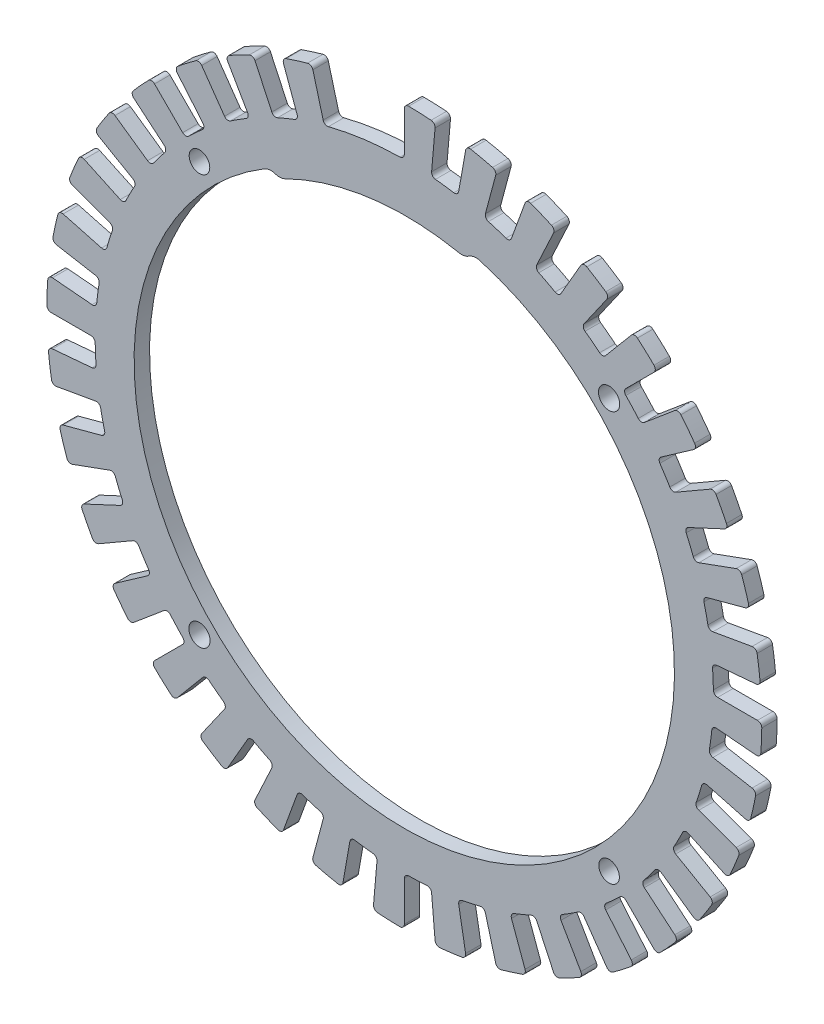
SolidWorks part; units mm, degrees
ref_plane "Front Plane" through (0, 0, 0) normal (0, 0, 1) x (1, 0, 0)
ref_plane "Top Plane" through (0, 0, 0) normal (0, 1, 0) x (1, 0, 0)
ref_plane "Right Plane" through (0, 0, 0) normal (1, 0, 0) x (0, 0, -1)
sketch "Sketch1" plane through (0, 0, 0) normal (0, 0, 1) x (1, 0, 0)
  line L0 (0, 82.7) -> (0, 71.5) construction
  line L1 (7.2078, 82.3853) -> (6.2316, 71.2279) construction
  line L2 (0, 71.5) -> (0, 0) construction
  line L3 (6.2316, 71.2279) -> (0, 0) construction
  line L4 (12.5883, 71.3918) -> (14.186, 80.4528) construction
  line L5 (12.5883, 71.3918) -> (0, 0) construction
  line L8 (0, 0) -> (47.3762, 47.3762) construction
  line L12 (50.5581, 50.5581) -> (47.3762, 47.3762) construction
  line L15 (47.3762, 47.3762) -> (44.1942, 44.1942) construction
  line L18 (7.3144, 72.1301) -> (6.3182, 72.2172) construction
  line L21 (7.3144, 72.1301) -> (7.2135, 71.1352) construction
  line L24 (12.5883, 71.3918) -> (11.6035, 71.5654) construction
  line L27 (11.6035, 71.5654) -> (11.4434, 70.5783) construction
  line L30 (1.0122, 82.6938) -> (1, 81.6939) construction
  line L33 (1, 81.6939) -> (0, 81.6939) construction
  line L36 (7.1201, 81.383) -> (6.1239, 81.4702) construction
  line L39 (6.1239, 81.4702) -> (6.1989, 82.4674) construction
  line L42 (7.1201, 81.383) -> (6.3182, 72.2172)
  line L45 (0, 81.6939) -> (0, 72.4931)
  line L48 (0, 72.4931) -> (-1, 72.4931) construction
  line L51 (-1, 72.4931) -> (-0.9862, 71.4932) construction
  line L109 (0, -82.7) -> (0, -71.5) [skipped]
  line L111 (14.3607, 81.4436) -> (12.4158, 70.4138) [skipped]
  line L115 (41.35, 71.6203) -> (35.75, 61.9208) [skipped]
  line L117 (53.1585, 63.3519) -> (45.9593, 54.7722) [skipped]
  line L118 (-63.3519, -53.1585) -> (-54.7722, -45.9593) [skipped]
  line L119 (63.3519, 53.1585) -> (54.7722, 45.9593) [skipped]
  line L121 (71.6203, 41.35) -> (61.9208, 35.75) [skipped]
  line L123 (77.7126, 28.2851) -> (67.188, 24.4544) [skipped]
  line L125 (81.4436, 14.3607) -> (70.4138, 12.4158) [skipped]
  line L127 (82.7, 0) -> (71.5, 0) [skipped]
  line L129 (81.4436, -14.3607) -> (70.4138, -12.4158) [skipped]
  line L131 (77.7126, -28.2851) -> (67.188, -24.4544) [skipped]
  line L133 (71.6203, -41.35) -> (61.9208, -35.75) [skipped]
  line L135 (63.3519, -53.1585) -> (54.7722, -45.9593) [skipped]
  line L137 (53.1585, -63.3519) -> (45.9593, -54.7722) [skipped]
  line L139 (41.35, -71.6203) -> (35.75, -61.9208) [skipped]
  line L141 (28.2851, -77.7126) -> (24.4544, -67.188) [skipped]
  line L142 (14.3607, -81.4436) -> (12.4158, -70.4138) [skipped]
  line L143 (34.9505, 74.9517) -> (30.2172, 64.801) [skipped]
  line L144 (47.4348, 67.7439) -> (41.0107, 58.5694) [skipped]
  line L145 (58.4777, 58.4777) -> (50.5581, 50.5581) [skipped]
  line L146 (67.7439, 47.4348) -> (58.5694, 41.0107) [skipped]
  line L147 (74.9517, 34.9505) -> (64.801, 30.2172) [skipped]
  line L148 (79.8821, 21.4043) -> (69.0637, 18.5056) [skipped]
  line L149 (82.3853, 7.2078) -> (71.2279, 6.2316) [skipped]
  line L150 (82.3853, -7.2078) -> (71.2279, -6.2316) [skipped]
  line L151 (79.8821, -21.4043) -> (69.0637, -18.5056) [skipped]
  line L152 (74.9517, -34.9505) -> (64.801, -30.2172) [skipped]
  line L153 (67.7439, -47.4348) -> (58.5694, -41.0107) [skipped]
  line L154 (58.4777, -58.4777) -> (50.5581, -50.5581) [skipped]
  line L155 (47.4348, -67.7439) -> (41.0107, -58.5694) [skipped]
  line L156 (34.9505, -74.9517) -> (30.2172, -64.801) [skipped]
  line L157 (21.4043, -79.8821) -> (18.5056, -69.0637) [skipped]
  line L158 (7.2078, -82.3853) -> (6.2316, -71.2279) [skipped]
  line L159 (-7.2078, -82.3853) -> (-6.2316, -71.2279) [skipped]
  line L160 (-21.4043, -79.8821) -> (-18.5056, -69.0637) [skipped]
  line L161 (-34.9505, -74.9517) -> (-30.2172, -64.801) [skipped]
  line L162 (-47.4348, -67.7439) -> (-41.0107, -58.5694) [skipped]
  line L163 (-58.4777, -58.4777) -> (-50.5581, -50.5581) [skipped]
  line L164 (-67.7439, -47.4348) -> (-58.5694, -41.0107) [skipped]
  line L165 (-74.9517, -34.9505) -> (-64.801, -30.2172) [skipped]
  line L166 (-79.8821, -21.4043) -> (-69.0637, -18.5056) [skipped]
  line L167 (-82.3853, -7.2078) -> (-71.2279, -6.2316) [skipped]
  line L168 (-82.3853, 7.2078) -> (-71.2279, 6.2316) [skipped]
  line L169 (-79.8821, 21.4043) -> (-69.0637, 18.5056) [skipped]
  line L170 (-74.9517, 34.9505) -> (-64.801, 30.2172) [skipped]
  line L171 (-67.7439, 47.4348) -> (-58.5694, 41.0107) [skipped]
  line L172 (-58.4777, 58.4777) -> (-50.5581, 50.5581) [skipped]
  line L173 (-47.4348, 67.7439) -> (-41.0107, 58.5694) [skipped]
  line L174 (-34.9505, 74.9517) -> (-30.2172, 64.801) [skipped]
  line L175 (-21.4043, 79.8821) -> (-18.5056, 69.0637) [skipped]
  line L176 (21.4043, 79.8821) -> (18.5056, 69.0637) [skipped]
  line L209 (0, 0) -> (-47.3762, -47.3762) construction
  line L210 (0, 0) -> (-47.3762, 47.3762) construction
  line L211 (0, 0) -> (47.3762, -47.3762) construction
  line L212 (14.186, 80.4528) -> (12.5883, 71.3918)
  line L213 (21.1439, 78.9102) -> (18.7626, 70.023)
  line L214 (27.941, 76.7671) -> (24.7941, 68.1212)
  line L215 (34.5253, 74.0398) -> (30.6369, 65.7011)
  line L216 (40.8469, 70.749) -> (36.2466, 62.7809)
  line L217 (46.8577, 66.9197) -> (41.5803, 59.3829)
  line L218 (52.5118, 62.5811) -> (46.5977, 55.5329)
  line L219 (57.7663, 57.7663) -> (51.2604, 51.2604)
  line L220 (62.5811, 52.5118) -> (55.5329, 46.5977)
  line L221 (66.9197, 46.8577) -> (59.3829, 41.5803)
  line L222 (70.749, 40.8469) -> (62.7809, 36.2466)
  line L223 (74.0398, 34.5253) -> (65.7011, 30.6369)
  line L224 (76.7671, 27.941) -> (68.1212, 24.7941)
  line L225 (78.9102, 21.1439) -> (70.023, 18.7626)
  line L226 (80.4528, 14.186) -> (71.3918, 12.5883)
  line L227 (81.383, 7.1201) -> (72.2172, 6.3182)
  line L228 (81.6939, 0) -> (72.4931, 0)
  line L229 (81.383, -7.1201) -> (72.2172, -6.3182)
  line L230 (80.4528, -14.186) -> (71.3918, -12.5883)
  line L231 (78.9102, -21.1439) -> (70.023, -18.7626)
  line L232 (76.7671, -27.941) -> (68.1212, -24.7941)
  line L233 (74.0398, -34.5253) -> (65.7011, -30.6369)
  line L234 (70.749, -40.8469) -> (62.7809, -36.2466)
  line L235 (66.9197, -46.8577) -> (59.3829, -41.5803)
  line L236 (62.5811, -52.5118) -> (55.5329, -46.5977)
  line L237 (57.7663, -57.7663) -> (51.2604, -51.2604)
  line L238 (52.5118, -62.5811) -> (46.5977, -55.5329)
  line L239 (46.8577, -66.9197) -> (41.5803, -59.3829)
  line L240 (40.8469, -70.749) -> (36.2466, -62.7809)
  line L241 (34.5253, -74.0398) -> (30.6369, -65.7011)
  line L242 (27.941, -76.7671) -> (24.7941, -68.1212)
  line L243 (21.1439, -78.9102) -> (18.7626, -70.023)
  line L244 (14.186, -80.4528) -> (12.5883, -71.3918)
  line L245 (7.1201, -81.383) -> (6.3182, -72.2172)
  line L246 (0, -81.6939) -> (0, -72.4931)
  line L247 (-7.1201, -81.383) -> (-6.3182, -72.2172)
  line L248 (-14.186, -80.4528) -> (-12.5883, -71.3918)
  line L249 (-21.1439, -78.9102) -> (-18.7626, -70.023)
  line L250 (-27.941, -76.7671) -> (-24.7941, -68.1212)
  line L251 (-34.5253, -74.0398) -> (-30.6369, -65.7011)
  line L252 (-40.8469, -70.749) -> (-36.2466, -62.7809)
  line L253 (-46.8577, -66.9197) -> (-41.5803, -59.3829)
  line L254 (-52.5118, -62.5811) -> (-46.5977, -55.5329)
  line L255 (-57.7663, -57.7663) -> (-51.2604, -51.2604)
  line L256 (-62.5811, -52.5118) -> (-55.5329, -46.5977)
  line L257 (-66.9197, -46.8577) -> (-59.3829, -41.5803)
  line L258 (-70.749, -40.8469) -> (-62.7809, -36.2466)
  line L259 (-74.0398, -34.5253) -> (-65.7011, -30.6369)
  line L260 (-76.7671, -27.941) -> (-68.1212, -24.7941)
  line L261 (-78.9102, -21.1439) -> (-70.023, -18.7626)
  line L262 (-80.4528, -14.186) -> (-71.3918, -12.5883)
  line L263 (-81.383, -7.1201) -> (-72.2172, -6.3182)
  line L264 (-81.6939, 0) -> (-72.4931, 0)
  line L265 (-81.383, 7.1201) -> (-72.2172, 6.3182)
  line L266 (-80.4528, 14.186) -> (-71.3918, 12.5883)
  line L267 (-78.9102, 21.1439) -> (-70.023, 18.7626)
  line L268 (-76.7671, 27.941) -> (-68.1212, 24.7941)
  line L269 (-74.0398, 34.5253) -> (-65.7011, 30.6369)
  line L270 (-70.749, 40.8469) -> (-62.7809, 36.2466)
  line L271 (-66.9197, 46.8577) -> (-59.3829, 41.5803)
  line L272 (-62.5811, 52.5118) -> (-55.5329, 46.5977)
  line L273 (-57.7663, 57.7663) -> (-51.2604, 51.2604)
  line L274 (-52.5118, 62.5811) -> (-46.5977, 55.5329)
  line L275 (-46.8577, 66.9197) -> (-41.5803, 59.3829)
  line L276 (-40.8469, 70.749) -> (-36.2466, 62.7809)
  line L277 (-34.5253, 74.0398) -> (-30.6369, 65.7011)
  line L278 (-27.941, 76.7671) -> (-24.7941, 68.1212)
  line L279 (-21.1439, 78.9102) -> (-18.7626, 70.023)
  line L280 (-0.9864, 71.4932) -> (-0.9862, 71.4932)
  line L281 (-32.3995, 53.4464) -> (-30.8444, 50.881) construction
  line L282 (-30.8444, 50.881) -> (-29.8635, 53.7161) construction
  line L283 (-29.8635, 53.7161) -> (-28.8826, 56.5512) construction
  line L284 (-28.8826, 56.5512) -> (-27.5181, 53.8795) construction
  line L285 (17.4626, 60.0109) -> (16.6244, 57.1304) construction
  line L286 (16.6244, 57.1304) -> (14.9432, 59.615) construction
  line L289 (13.262, 62.0997) -> (14.9432, 59.615) construction
  line L290 (-7.4414, 56.5227) -> (0, 0) construction
  line L291 (-27.5181, 53.8795) -> (-7.4414, 56.5227) construction
  line L292 (-7.4414, 56.5227) -> (12.6354, 59.1658) construction
  line L293 (13.262, 62.0997) -> (12.6354, 59.1658) construction
  line L294 (-28.4278, 55.6607) -> (13.0531, 61.1217) construction
  circle A0 centre (0, 0) radius 82.7 construction
  arc A1 (-32.3995, 53.4464) -> (17.4626, 60.0109) centre (0, 0) ccw
  circle A73 centre (47.3762, 47.3762) radius 2.4585
  circle A74 centre (47.3762, 47.3762) radius 2.987 construction
  arc A78 (0, 71.5) -> (6.2316, 71.2279) centre (0, 0) cw construction
  arc A79 (6.3182, 72.2172) -> (7.2135, 71.1352) centre (7.3144, 72.1301) ccw
  arc A80 (11.4434, 70.5783) -> (12.5883, 71.3918) centre (11.6035, 71.5654) ccw construction
  arc A81 (7.1201, 81.383) -> (6.1989, 82.4674) centre (6.1239, 81.4702) ccw
  arc A82 (0, 81.6939) -> (1.0122, 82.6938) centre (1, 81.6939) cw
  arc A83 (6.5367, 74.7146) -> (13.0236, 73.8606) centre (0, 0) cw [skipped]
  arc A84 (7.2135, 71.1352) -> (11.4434, 70.5783) centre (0, 0) cw
  arc A85 (0, 82.7) -> (7.2078, 82.3853) centre (0, 0) cw [skipped]
  arc A86 (1.0122, 82.6938) -> (6.1989, 82.4674) centre (0, 0) cw
  arc A87 (28.2851, 77.7126) -> (34.9505, 74.9517) centre (0, 0) cw [skipped]
  arc A88 (31.6964, 67.9731) -> (37.5, 64.9519) centre (0, 0) cw [skipped]
  arc A89 (41.35, 71.6203) -> (47.4348, 67.7439) centre (0, 0) cw [skipped]
  arc A90 (43.0182, 61.4364) -> (48.2091, 57.4533) centre (0, 0) cw [skipped]
  arc A91 (53.1585, 63.3519) -> (58.4777, 58.4777) centre (0, 0) cw [skipped]
  arc A92 (53.033, 53.033) -> (57.4533, 48.2091) centre (0, 0) cw [skipped]
  arc A93 (63.3519, 53.1585) -> (67.7439, 47.4348) centre (0, 0) cw [skipped]
  arc A94 (61.4364, 43.0182) -> (64.9519, 37.5) centre (0, 0) cw [skipped]
  arc A95 (71.6203, 41.35) -> (74.9517, 34.9505) centre (0, 0) cw [skipped]
  arc A96 (67.9731, 31.6964) -> (70.4769, 25.6515) centre (0, 0) cw [skipped]
  arc A97 (77.7126, 28.2851) -> (79.8821, 21.4043) centre (0, 0) cw [skipped]
  arc A98 (72.4444, 19.4114) -> (73.8606, 13.0236) centre (0, 0) cw [skipped]
  arc A99 (81.4436, 14.3607) -> (82.3853, 7.2078) centre (0, 0) cw [skipped]
  arc A100 (74.7146, 6.5367) -> (75, 0) centre (0, 0) cw [skipped]
  arc A101 (82.7, 0) -> (82.3853, -7.2078) centre (0, 0) cw [skipped]
  arc A102 (74.7146, -6.5367) -> (73.8606, -13.0236) centre (0, 0) cw [skipped]
  arc A103 (81.4436, -14.3607) -> (79.8821, -21.4043) centre (0, 0) cw [skipped]
  arc A104 (72.4444, -19.4114) -> (70.4769, -25.6515) centre (0, 0) cw [skipped]
  arc A105 (77.7126, -28.2851) -> (74.9517, -34.9505) centre (0, 0) cw [skipped]
  arc A106 (67.9731, -31.6964) -> (64.9519, -37.5) centre (0, 0) cw [skipped]
  arc A107 (71.6203, -41.35) -> (67.7439, -47.4348) centre (0, 0) cw [skipped]
  arc A108 (61.4364, -43.0182) -> (57.4533, -48.2091) centre (0, 0) cw [skipped]
  arc A109 (63.3519, -53.1585) -> (58.4777, -58.4777) centre (0, 0) cw [skipped]
  arc A110 (53.033, -53.033) -> (48.2091, -57.4533) centre (0, 0) cw [skipped]
  arc A111 (53.1585, -63.3519) -> (47.4348, -67.7439) centre (0, 0) cw [skipped]
  arc A112 (43.0182, -61.4364) -> (37.5, -64.9519) centre (0, 0) cw [skipped]
  arc A113 (41.35, -71.6203) -> (34.9505, -74.9517) centre (0, 0) cw [skipped]
  arc A114 (31.6964, -67.9731) -> (25.6515, -70.4769) centre (0, 0) cw [skipped]
  arc A115 (28.2851, -77.7126) -> (21.4043, -79.8821) centre (0, 0) cw [skipped]
  arc A116 (19.4114, -72.4444) -> (13.0236, -73.8606) centre (0, 0) cw [skipped]
  arc A117 (14.3607, -81.4436) -> (7.2078, -82.3853) centre (0, 0) cw [skipped]
  arc A118 (6.5367, -74.7146) -> (0, -75) centre (0, 0) cw [skipped]
  arc A119 (0, -82.7) -> (-7.2078, -82.3853) centre (0, 0) cw [skipped]
  arc A120 (-6.5367, -74.7146) -> (-13.0236, -73.8606) centre (0, 0) cw [skipped]
  arc A121 (-14.3607, -81.4436) -> (-21.4043, -79.8821) centre (0, 0) cw [skipped]
  arc A122 (-28.2851, -77.7126) -> (-34.9505, -74.9517) centre (0, 0) cw [skipped]
  arc A123 (-19.4114, -72.4444) -> (-25.6515, -70.4769) centre (0, 0) cw [skipped]
  arc A124 (-31.6964, -67.9731) -> (-37.5, -64.9519) centre (0, 0) cw [skipped]
  arc A125 (-41.35, -71.6203) -> (-47.4348, -67.7439) centre (0, 0) cw [skipped]
  arc A126 (-43.0182, -61.4364) -> (-48.2091, -57.4533) centre (0, 0) cw [skipped]
  arc A127 (-53.1585, -63.3519) -> (-58.4777, -58.4777) centre (0, 0) cw [skipped]
  arc A128 (-53.033, -53.033) -> (-57.4533, -48.2091) centre (0, 0) cw [skipped]
  arc A129 (-63.3519, -53.1585) -> (-67.7439, -47.4348) centre (0, 0) cw [skipped]
  arc A130 (-61.4364, -43.0182) -> (-64.9519, -37.5) centre (0, 0) cw [skipped]
  arc A131 (-71.6203, -41.35) -> (-74.9517, -34.9505) centre (0, 0) cw [skipped]
  arc A132 (-67.9731, -31.6964) -> (-70.4769, -25.6515) centre (0, 0) cw [skipped]
  arc A133 (-77.7126, -28.2851) -> (-79.8821, -21.4043) centre (0, 0) cw [skipped]
  arc A134 (-72.4444, -19.4114) -> (-73.8606, -13.0236) centre (0, 0) cw [skipped]
  arc A135 (-81.4436, -14.3607) -> (-82.3853, -7.2078) centre (0, 0) cw [skipped]
  arc A136 (-74.7146, -6.5367) -> (-75, 0) centre (0, 0) cw [skipped]
  arc A137 (-82.7, 0) -> (-82.3853, 7.2078) centre (0, 0) cw [skipped]
  arc A138 (-74.7146, 6.5367) -> (-73.8606, 13.0236) centre (0, 0) cw [skipped]
  arc A139 (-81.4436, 14.3607) -> (-79.8821, 21.4043) centre (0, 0) cw [skipped]
  arc A140 (-72.4444, 19.4114) -> (-70.4769, 25.6515) centre (0, 0) cw [skipped]
  arc A141 (-77.7126, 28.2851) -> (-74.9517, 34.9505) centre (0, 0) cw [skipped]
  arc A142 (-67.9731, 31.6964) -> (-64.9519, 37.5) centre (0, 0) cw [skipped]
  arc A143 (-71.6203, 41.35) -> (-67.7439, 47.4348) centre (0, 0) cw [skipped]
  arc A144 (-61.4364, 43.0182) -> (-57.4533, 48.2091) centre (0, 0) cw [skipped]
  arc A145 (-63.3519, 53.1585) -> (-58.4777, 58.4777) centre (0, 0) cw [skipped]
  arc A146 (-53.033, 53.033) -> (-48.2091, 57.4533) centre (0, 0) cw [skipped]
  arc A147 (-53.1585, 63.3519) -> (-47.4348, 67.7439) centre (0, 0) cw [skipped]
  arc A148 (-43.0182, 61.4364) -> (-37.5, 64.9519) centre (0, 0) cw [skipped]
  arc A149 (-41.35, 71.6203) -> (-34.9505, 74.9517) centre (0, 0) cw [skipped]
  arc A150 (-31.6964, 67.9731) -> (-25.6515, 70.4769) centre (0, 0) cw [skipped]
  arc A151 (-28.2851, 77.7126) -> (-21.4043, 79.8821) centre (0, 0) cw [skipped]
  arc A152 (-19.4114, 72.4444) -> (-13.0236, 73.8606) centre (0, 0) cw [skipped]
  arc A153 (14.3607, 81.4436) -> (21.4043, 79.8821) centre (0, 0) cw [skipped]
  arc A154 (19.4114, 72.4444) -> (25.6515, 70.4769) centre (0, 0) cw [skipped]
  arc A155 (0, 72.4931) -> (-0.9862, 71.4932) centre (-1, 72.4931) cw
  circle A367 centre (-47.3762, -47.3762) radius 2.4585
  circle A368 centre (47.3762, -47.3762) radius 2.3812
  circle A369 centre (-47.3762, 47.3762) radius 2.3813
  circle A370 centre (0, 0) radius 71.5 construction
  arc A371 (12.5883, 71.3918) -> (11.4434, 70.5783) centre (11.6035, 71.5654) cw
  arc A372 (14.186, 80.4528) -> (15.3565, 81.2617) centre (15.1708, 80.2791) cw
  arc A373 (15.3565, 81.2617) -> (20.425, 80.1381) centre (0, 0) cw
  arc A374 (21.1439, 78.9102) -> (20.425, 80.1381) centre (20.178, 79.169) ccw
  arc A375 (18.7626, 70.023) -> (19.4564, 68.8019) centre (19.7285, 69.7641) ccw
  arc A376 (19.4564, 68.8019) -> (23.5254, 67.5189) centre (0, 0) cw
  arc A377 (24.7941, 68.1212) -> (23.5254, 67.5189) centre (23.8544, 68.4633) cw
  arc A378 (27.941, 76.7671) -> (29.2341, 77.3606) centre (28.8806, 76.4251) cw
  arc A379 (29.2341, 77.3606) -> (34.0305, 75.3738) centre (0, 0) cw
  arc A380 (34.5253, 74.0398) -> (34.0305, 75.3738) centre (33.619, 74.4624) ccw
  arc A381 (30.6369, 65.7011) -> (31.1081, 64.3781) centre (31.5432, 65.2784) ccw
  arc A382 (31.1081, 64.3781) -> (34.8925, 62.408) centre (0, 0) cw
  arc A384 (36.2466, 62.7809) -> (34.8925, 62.408) centre (35.3805, 63.2809) cw
  arc A385 (40.8469, 70.749) -> (42.2235, 71.1088) centre (41.713, 70.249) cw
  arc A386 (42.2235, 71.1088) -> (46.602, 68.3194) centre (0, 0) cw
  arc A387 (46.8577, 66.9197) -> (46.602, 68.3194) centre (46.0385, 67.4933) ccw
  arc A388 (41.5803, 59.3829) -> (41.8147, 57.9981) centre (42.3995, 58.8093) ccw
  arc A389 (41.8147, 57.9981) -> (45.1995, 55.4009) centre (0, 0) cw
  arc A390 (46.5977, 55.5329) -> (45.1995, 55.4009) centre (45.8316, 56.1757) cw
  arc A391 (52.5118, 62.5811) -> (53.93, 62.6965) centre (53.2779, 61.9384) cw
  arc A392 (53.93, 62.6965) -> (57.7576, 59.1891) centre (0, 0) cw
  arc A393 (57.7663, 57.7663) -> (57.7576, 59.1891) centre (57.0592, 58.4734) ccw
  arc A394 (51.2604, 51.2604) -> (51.2507, 49.856) centre (51.9675, 50.5533) ccw
  arc A395 (51.2507, 49.856) -> (54.133, 46.7104) centre (0, 0) cw
  arc A396 (55.5329, 46.5977) -> (54.133, 46.7104) centre (54.8902, 47.3637) cw
  arc A397 (62.5811, 52.5118) -> (63.9978, 52.3791) centre (63.2239, 51.7458) cw
  arc A398 (63.9978, 52.3791) -> (67.1582, 48.2604) centre (0, 0) cw
  arc A399 (66.9197, 46.8577) -> (67.1582, 48.2604) centre (66.3461, 47.6768) ccw
  arc A400 (59.3829, 41.5803) -> (59.1295, 40.199) centre (59.9565, 40.7612) ccw
  arc A401 (59.1295, 40.199) -> (61.4218, 36.6007) centre (0, 0) cw
  arc A402 (62.7809, 36.2466) -> (61.4218, 36.6007) centre (62.2809, 37.1126) cw
  arc A403 (70.749, 40.8469) -> (72.1211, 40.4703) centre (71.249, 39.9809) cw
  arc A404 (72.1211, 40.4703) -> (74.5182, 35.8653) centre (0, 0) cw
  arc A405 (74.0398, 34.5253) -> (74.5182, 35.8653) centre (73.6172, 35.4316) ccw
  arc A406 (65.7011, 30.6369) -> (65.2116, 29.3205) centre (66.1237, 29.7306) ccw
  arc A407 (65.2116, 29.3205) -> (66.8443, 25.3788) centre (0, 0) cw
  arc A408 (68.1212, 24.7941) -> (66.8443, 25.3788) centre (67.7792, 25.7338) cw
  arc A409 (76.7671, 27.941) -> (78.053, 27.3318) centre (77.1092, 27.0013) cw
  arc A410 (78.053, 27.3318) -> (79.6141, 22.3805) centre (0, 0) cw
  arc A411 (78.9102, 21.1439) -> (79.6141, 22.3805) centre (78.6514, 22.1099) ccw
  arc A412 (70.023, 18.7626) -> (69.3124, 17.5512) centre (70.2818, 17.7967) ccw
  arc A413 (69.3124, 17.5512) -> (70.2358, 13.3859) centre (0, 0) cw
  arc A414 (71.3918, 12.5883) -> (70.2358, 13.3859) centre (71.2181, 13.5731) cw
  arc A415 (80.4528, 14.186) -> (81.6133, 13.3628) centre (80.6264, 13.2012) cw
  arc A416 (81.6133, 13.3628) -> (82.2909, 8.2156) centre (0, 0) cw
  arc A417 (81.383, 7.1201) -> (82.2909, 8.2156) centre (81.2959, 8.1163) ccw
  arc A418 (72.2172, 6.3182) -> (71.3071, 5.2486) centre (72.3044, 5.322) ccw
  arc A419 (71.3071, 5.2486) -> (71.4932, 0.9862) centre (0, 0) cw
  arc A420 (72.4931, 0) -> (71.4932, 0.9862) centre (72.4931, 1) cw
  arc A421 (81.6939, 0) -> (82.6938, -1.0122) centre (81.6939, -1) cw
  arc A422 (82.6938, -1.0122) -> (82.4674, -6.1989) centre (0, 0) cw
  arc A423 (81.383, -7.1201) -> (82.4674, -6.1989) centre (81.4702, -6.1239) ccw
  arc A424 (72.2172, -6.3182) -> (71.1352, -7.2135) centre (72.1301, -7.3144) ccw
  arc A425 (71.1352, -7.2135) -> (70.5783, -11.4434) centre (0, 0) cw
  arc A426 (71.3918, -12.5883) -> (70.5783, -11.4434) centre (71.5654, -11.6035) cw
  arc A427 (80.4528, -14.186) -> (81.2617, -15.3565) centre (80.2791, -15.1708) cw
  arc A428 (81.2617, -15.3565) -> (80.1381, -20.425) centre (0, 0) cw
  arc A429 (78.9102, -21.1439) -> (80.1381, -20.425) centre (79.169, -20.178) ccw
  arc A430 (70.023, -18.7626) -> (68.8019, -19.4564) centre (69.7641, -19.7285) ccw
  arc A431 (68.8019, -19.4564) -> (67.5189, -23.5254) centre (0, 0) cw
  arc A432 (68.1212, -24.7941) -> (67.5189, -23.5254) centre (68.4633, -23.8544) cw
  arc A433 (76.7671, -27.941) -> (77.3606, -29.2341) centre (76.4251, -28.8806) cw
  arc A434 (77.3606, -29.2341) -> (75.3738, -34.0305) centre (0, 0) cw
  arc A435 (74.0398, -34.5253) -> (75.3738, -34.0305) centre (74.4624, -33.619) ccw
  arc A436 (65.7011, -30.6369) -> (64.3781, -31.1081) centre (65.2784, -31.5432) ccw
  arc A437 (64.3781, -31.1081) -> (62.408, -34.8925) centre (0, 0) cw
  arc A438 (62.7809, -36.2466) -> (62.408, -34.8925) centre (63.2809, -35.3805) cw
  arc A439 (70.749, -40.8469) -> (71.1088, -42.2235) centre (70.249, -41.713) cw
  arc A440 (71.1088, -42.2235) -> (68.3194, -46.602) centre (0, 0) cw
  arc A441 (66.9197, -46.8577) -> (68.3194, -46.602) centre (67.4933, -46.0385) ccw
  arc A442 (59.3829, -41.5803) -> (57.9981, -41.8147) centre (58.8093, -42.3995) ccw
  arc A443 (57.9981, -41.8147) -> (55.4009, -45.1995) centre (0, 0) cw
  arc A444 (55.5329, -46.5977) -> (55.4009, -45.1995) centre (56.1757, -45.8316) cw
  arc A445 (62.5811, -52.5118) -> (62.6965, -53.93) centre (61.9384, -53.2779) cw
  arc A446 (62.6965, -53.93) -> (59.1891, -57.7576) centre (0, 0) cw
  arc A447 (57.7663, -57.7663) -> (59.1891, -57.7576) centre (58.4734, -57.0592) ccw
  arc A448 (51.2604, -51.2604) -> (49.856, -51.2507) centre (50.5533, -51.9675) ccw
  arc A449 (49.856, -51.2507) -> (46.7104, -54.133) centre (0, 0) cw
  arc A450 (46.5977, -55.5329) -> (46.7104, -54.133) centre (47.3637, -54.8902) cw
  arc A451 (52.5118, -62.5811) -> (52.3791, -63.9978) centre (51.7458, -63.2239) cw
  arc A452 (52.3791, -63.9978) -> (48.2604, -67.1582) centre (0, 0) cw
  arc A453 (46.8577, -66.9197) -> (48.2604, -67.1582) centre (47.6768, -66.3461) ccw
  arc A454 (41.5803, -59.3829) -> (40.199, -59.1295) centre (40.7612, -59.9565) ccw
  arc A455 (40.199, -59.1295) -> (36.6007, -61.4218) centre (0, 0) cw
  arc A456 (36.2466, -62.7809) -> (36.6007, -61.4218) centre (37.1126, -62.2809) cw
  arc A457 (40.8469, -70.749) -> (40.4703, -72.1211) centre (39.9809, -71.249) cw
  arc A458 (40.4703, -72.1211) -> (35.8653, -74.5182) centre (0, 0) cw
  arc A459 (34.5253, -74.0398) -> (35.8653, -74.5182) centre (35.4316, -73.6172) ccw
  arc A460 (30.6369, -65.7011) -> (29.3205, -65.2116) centre (29.7306, -66.1237) ccw
  arc A461 (29.3205, -65.2116) -> (25.3788, -66.8443) centre (0, 0) cw
  arc A462 (24.7941, -68.1212) -> (25.3788, -66.8443) centre (25.7338, -67.7792) cw
  arc A463 (27.941, -76.7671) -> (27.3318, -78.053) centre (27.0013, -77.1092) cw
  arc A464 (27.3318, -78.053) -> (22.3805, -79.6141) centre (0, 0) cw
  arc A465 (21.1439, -78.9102) -> (22.3805, -79.6141) centre (22.1099, -78.6514) ccw
  arc A466 (18.7626, -70.023) -> (17.5512, -69.3124) centre (17.7967, -70.2818) ccw
  arc A467 (17.5512, -69.3124) -> (13.3859, -70.2358) centre (0, 0) cw
  arc A468 (12.5883, -71.3918) -> (13.3859, -70.2358) centre (13.5731, -71.2181) cw
  arc A469 (14.186, -80.4528) -> (13.3628, -81.6133) centre (13.2012, -80.6264) cw
  arc A470 (13.3628, -81.6133) -> (8.2156, -82.2909) centre (0, 0) cw
  arc A471 (7.1201, -81.383) -> (8.2156, -82.2909) centre (8.1163, -81.2959) ccw
  arc A472 (6.3182, -72.2172) -> (5.2486, -71.3071) centre (5.322, -72.3044) ccw
  arc A473 (5.2486, -71.3071) -> (0.9862, -71.4932) centre (0, 0) cw
  arc A474 (0, -72.4931) -> (0.9862, -71.4932) centre (1, -72.4931) cw
  arc A475 (0, -81.6939) -> (-1.0122, -82.6938) centre (-1, -81.6939) cw
  arc A476 (-1.0122, -82.6938) -> (-6.1989, -82.4674) centre (0, 0) cw
  arc A477 (-7.1201, -81.383) -> (-6.1989, -82.4674) centre (-6.1239, -81.4702) ccw
  arc A478 (-6.3182, -72.2172) -> (-7.2135, -71.1352) centre (-7.3144, -72.1301) ccw
  arc A479 (-7.2135, -71.1352) -> (-11.4434, -70.5783) centre (0, 0) cw
  arc A480 (-12.5883, -71.3918) -> (-11.4434, -70.5783) centre (-11.6035, -71.5654) cw
  arc A481 (-14.186, -80.4528) -> (-15.3565, -81.2617) centre (-15.1708, -80.2791) cw
  arc A482 (-15.3565, -81.2617) -> (-20.425, -80.1381) centre (0, 0) cw
  arc A483 (-21.1439, -78.9102) -> (-20.425, -80.1381) centre (-20.178, -79.169) ccw
  arc A484 (-18.7626, -70.023) -> (-19.4564, -68.8019) centre (-19.7285, -69.7641) ccw
  arc A485 (-19.4564, -68.8019) -> (-23.5254, -67.5189) centre (0, 0) cw
  arc A486 (-24.7941, -68.1212) -> (-23.5254, -67.5189) centre (-23.8544, -68.4633) cw
  arc A487 (-27.941, -76.7671) -> (-29.2341, -77.3606) centre (-28.8806, -76.4251) cw
  arc A488 (-29.2341, -77.3606) -> (-34.0305, -75.3738) centre (0, 0) cw
  arc A489 (-34.5253, -74.0398) -> (-34.0305, -75.3738) centre (-33.619, -74.4624) ccw
  arc A490 (-30.6369, -65.7011) -> (-31.1081, -64.3781) centre (-31.5432, -65.2784) ccw
  arc A491 (-31.1081, -64.3781) -> (-34.8925, -62.408) centre (0, 0) cw
  arc A492 (-36.2466, -62.7809) -> (-34.8925, -62.408) centre (-35.3805, -63.2809) cw
  arc A493 (-40.8469, -70.749) -> (-42.2235, -71.1088) centre (-41.713, -70.249) cw
  arc A494 (-42.2235, -71.1088) -> (-46.602, -68.3194) centre (0, 0) cw
  arc A495 (-46.8577, -66.9197) -> (-46.602, -68.3194) centre (-46.0385, -67.4933) ccw
  arc A496 (-41.5803, -59.3829) -> (-41.8147, -57.9981) centre (-42.3995, -58.8093) ccw
  arc A497 (-41.8147, -57.9981) -> (-45.1995, -55.4009) centre (0, 0) cw
  arc A498 (-46.5977, -55.5329) -> (-45.1995, -55.4009) centre (-45.8316, -56.1757) cw
  arc A499 (-52.5118, -62.5811) -> (-53.93, -62.6965) centre (-53.2779, -61.9384) cw
  arc A500 (-53.93, -62.6965) -> (-57.7576, -59.1891) centre (0, 0) cw
  arc A501 (-57.7663, -57.7663) -> (-57.7576, -59.1891) centre (-57.0592, -58.4734) ccw
  arc A502 (-51.2604, -51.2604) -> (-51.2507, -49.856) centre (-51.9675, -50.5533) ccw
  arc A503 (-51.2507, -49.856) -> (-54.133, -46.7104) centre (0, 0) cw
  arc A504 (-55.5329, -46.5977) -> (-54.133, -46.7104) centre (-54.8902, -47.3637) cw
  arc A505 (-62.5811, -52.5118) -> (-63.9978, -52.3791) centre (-63.2239, -51.7458) cw
  arc A506 (-63.9978, -52.3791) -> (-67.1582, -48.2604) centre (0, 0) cw
  arc A507 (-66.9197, -46.8577) -> (-67.1582, -48.2604) centre (-66.3461, -47.6768) ccw
  arc A508 (-59.3829, -41.5803) -> (-59.1295, -40.199) centre (-59.9565, -40.7612) ccw
  arc A509 (-59.1295, -40.199) -> (-61.4218, -36.6007) centre (0, 0) cw
  arc A510 (-62.7809, -36.2466) -> (-61.4218, -36.6007) centre (-62.2809, -37.1126) cw
  arc A511 (-70.749, -40.8469) -> (-72.1211, -40.4703) centre (-71.249, -39.9809) cw
  arc A512 (-72.1211, -40.4703) -> (-74.5182, -35.8653) centre (0, 0) cw
  arc A513 (-74.0398, -34.5253) -> (-74.5182, -35.8653) centre (-73.6172, -35.4316) ccw
  arc A514 (-65.7011, -30.6369) -> (-65.2116, -29.3205) centre (-66.1237, -29.7306) ccw
  arc A515 (-65.2116, -29.3205) -> (-66.8443, -25.3788) centre (0, 0) cw
  arc A516 (-68.1212, -24.7941) -> (-66.8443, -25.3788) centre (-67.7792, -25.7338) cw
  arc A517 (-76.7671, -27.941) -> (-78.053, -27.3318) centre (-77.1092, -27.0013) cw
  arc A518 (-78.053, -27.3318) -> (-79.6141, -22.3805) centre (0, 0) cw
  arc A519 (-78.9102, -21.1439) -> (-79.6141, -22.3805) centre (-78.6514, -22.1099) ccw
  arc A520 (-70.023, -18.7626) -> (-69.3124, -17.5512) centre (-70.2818, -17.7967) ccw
  arc A521 (-69.3124, -17.5512) -> (-70.2358, -13.3859) centre (0, 0) cw
  arc A522 (-71.3918, -12.5883) -> (-70.2358, -13.3859) centre (-71.2181, -13.5731) cw
  arc A523 (-80.4528, -14.186) -> (-81.6133, -13.3628) centre (-80.6264, -13.2012) cw
  arc A524 (-81.6133, -13.3628) -> (-82.2909, -8.2156) centre (0, 0) cw
  arc A525 (-81.383, -7.1201) -> (-82.2909, -8.2156) centre (-81.2959, -8.1163) ccw
  arc A526 (-72.2172, -6.3182) -> (-71.3071, -5.2486) centre (-72.3044, -5.322) ccw
  arc A527 (-71.3071, -5.2486) -> (-71.4932, -0.9862) centre (0, 0) cw
  arc A528 (-72.4931, 0) -> (-71.4932, -0.9862) centre (-72.4931, -1) cw
  arc A529 (-81.6939, 0) -> (-82.6938, 1.0122) centre (-81.6939, 1) cw
  arc A530 (-82.6938, 1.0122) -> (-82.4674, 6.1989) centre (0, 0) cw
  arc A531 (-81.383, 7.1201) -> (-82.4674, 6.1989) centre (-81.4702, 6.1239) ccw
  arc A532 (-72.2172, 6.3182) -> (-71.1352, 7.2135) centre (-72.1301, 7.3144) ccw
  arc A533 (-71.1352, 7.2135) -> (-70.5783, 11.4434) centre (0, 0) cw
  arc A534 (-71.3918, 12.5883) -> (-70.5783, 11.4434) centre (-71.5654, 11.6035) cw
  arc A535 (-80.4528, 14.186) -> (-81.2617, 15.3565) centre (-80.2791, 15.1708) cw
  arc A536 (-81.2617, 15.3565) -> (-80.1381, 20.425) centre (0, 0) cw
  arc A537 (-78.9102, 21.1439) -> (-80.1381, 20.425) centre (-79.169, 20.178) ccw
  arc A538 (-70.023, 18.7626) -> (-68.8019, 19.4564) centre (-69.7641, 19.7285) ccw
  arc A539 (-68.8019, 19.4564) -> (-67.5189, 23.5254) centre (0, 0) cw
  arc A540 (-68.1212, 24.7941) -> (-67.5189, 23.5254) centre (-68.4633, 23.8544) cw
  arc A541 (-76.7671, 27.941) -> (-77.3606, 29.2341) centre (-76.4251, 28.8806) cw
  arc A542 (-77.3606, 29.2341) -> (-75.3738, 34.0305) centre (0, 0) cw
  arc A543 (-74.0398, 34.5253) -> (-75.3738, 34.0305) centre (-74.4624, 33.619) ccw
  arc A544 (-65.7011, 30.6369) -> (-64.3781, 31.1081) centre (-65.2784, 31.5432) ccw
  arc A545 (-64.3781, 31.1081) -> (-62.408, 34.8925) centre (0, 0) cw
  arc A546 (-62.7809, 36.2466) -> (-62.408, 34.8925) centre (-63.2809, 35.3805) cw
  arc A547 (-70.749, 40.8469) -> (-71.1088, 42.2235) centre (-70.249, 41.713) cw
  arc A548 (-71.1088, 42.2235) -> (-68.3194, 46.602) centre (0, 0) cw
  arc A549 (-66.9197, 46.8577) -> (-68.3194, 46.602) centre (-67.4933, 46.0385) ccw
  arc A550 (-59.3829, 41.5803) -> (-57.9981, 41.8147) centre (-58.8093, 42.3995) ccw
  arc A551 (-57.9981, 41.8147) -> (-55.4009, 45.1995) centre (0, 0) cw
  arc A552 (-55.5329, 46.5977) -> (-55.4009, 45.1995) centre (-56.1757, 45.8316) cw
  arc A553 (-62.5811, 52.5118) -> (-62.6965, 53.93) centre (-61.9384, 53.2779) cw
  arc A554 (-62.6965, 53.93) -> (-59.1891, 57.7576) centre (0, 0) cw
  arc A555 (-57.7663, 57.7663) -> (-59.1891, 57.7576) centre (-58.4734, 57.0592) ccw
  arc A556 (-51.2604, 51.2604) -> (-49.856, 51.2507) centre (-50.5533, 51.9675) ccw
  arc A557 (-49.856, 51.2507) -> (-46.7104, 54.133) centre (0, 0) cw
  arc A558 (-46.5977, 55.5329) -> (-46.7104, 54.133) centre (-47.3637, 54.8902) cw
  arc A559 (-52.5118, 62.5811) -> (-52.3791, 63.9978) centre (-51.7458, 63.2239) cw
  arc A560 (-52.3791, 63.9978) -> (-48.2604, 67.1582) centre (0, 0) cw
  arc A561 (-46.8577, 66.9197) -> (-48.2604, 67.1582) centre (-47.6768, 66.3461) ccw
  arc A562 (-41.5803, 59.3829) -> (-40.199, 59.1295) centre (-40.7612, 59.9565) ccw
  arc A563 (-40.199, 59.1295) -> (-36.6007, 61.4218) centre (0, 0) cw
  arc A564 (-36.2466, 62.7809) -> (-36.6007, 61.4218) centre (-37.1126, 62.2809) cw
  arc A565 (-40.8469, 70.749) -> (-40.4703, 72.1211) centre (-39.9809, 71.249) cw
  arc A566 (-40.4703, 72.1211) -> (-35.8653, 74.5182) centre (0, 0) cw
  arc A567 (-34.5253, 74.0398) -> (-35.8653, 74.5182) centre (-35.4316, 73.6172) ccw
  arc A568 (-30.6369, 65.7011) -> (-29.3205, 65.2116) centre (-29.7306, 66.1237) ccw
  arc A569 (-29.3205, 65.2116) -> (-25.3788, 66.8443) centre (0, 0) cw
  arc A570 (-24.7941, 68.1212) -> (-25.3788, 66.8443) centre (-25.7338, 67.7792) cw
  arc A571 (-27.941, 76.7671) -> (-27.3318, 78.053) centre (-27.0013, 77.1092) cw
  arc A572 (-27.3318, 78.053) -> (-22.3805, 79.6141) centre (0, 0) cw
  arc A573 (-21.1439, 78.9102) -> (-22.3805, 79.6141) centre (-22.1099, 78.6514) ccw
  arc A574 (-18.7626, 70.023) -> (-17.5512, 69.3124) centre (-17.7967, 70.2818) ccw
  arc A575 (-17.5512, 69.3124) -> (-13.3859, 70.2358) centre (0, 0) cw
  arc A576 (-13.3859, 70.2358) -> (-0.9864, 71.4932) centre (0, 0) cw
  arc A577 (-29.8635, 53.7161) -> (-32.3995, 53.4464) centre (-30.8444, 50.881) ccw
  arc A578 (-29.8635, 53.7161) -> (-27.5181, 53.8795) centre (-28.8826, 56.5512) ccw
  arc A579 (17.4626, 60.0109) -> (14.9432, 59.615) centre (16.6244, 57.1304) ccw
  arc A580 (14.9432, 59.615) -> (12.6354, 59.1658) centre (13.262, 62.0997) cw
  circle A582 centre (0, 0) radius 62.5 construction
  arc A586 (-27.5181, 53.8795) -> (12.6354, 59.1658) centre (0.3099, -2.3542) cw
  point P3 (-28.4278, 55.6607)
  point P29 (0, 0)
  point P133 (13.0531, 61.1217)
  point P252 (0, 0)
  point P728 (0, 0)
  point P763 (0, 0)
  dimension "D2" = 165.4
  dimension "D7" = 4.917
  dimension "D8" = 5.974
  dimension "D12" = 1
  dimension "D14" = 11.2
  dimension "D15" = 11.2
  dimension "D17" = 2
  dimension "D20" = 4.7625
  dimension "D21" = 4.917
  dimension "D22" = 4.7625
  dimension "D3" = 5
  dimension "D4" = 67
  dimension "D6" = 45
  dimension "D10" = 67
  dimension "D11" = 5
  dimension "D9" = 4.5
  dimension "D16" = 7.5
  dimension "D18" = 40.5
  dimension "D19" = 3
  dimension "D5" = 35
  dimension "D13" = 35
extrude "Boss-Extrude1" add sketch "Sketch1" along normal blind 3.5719
